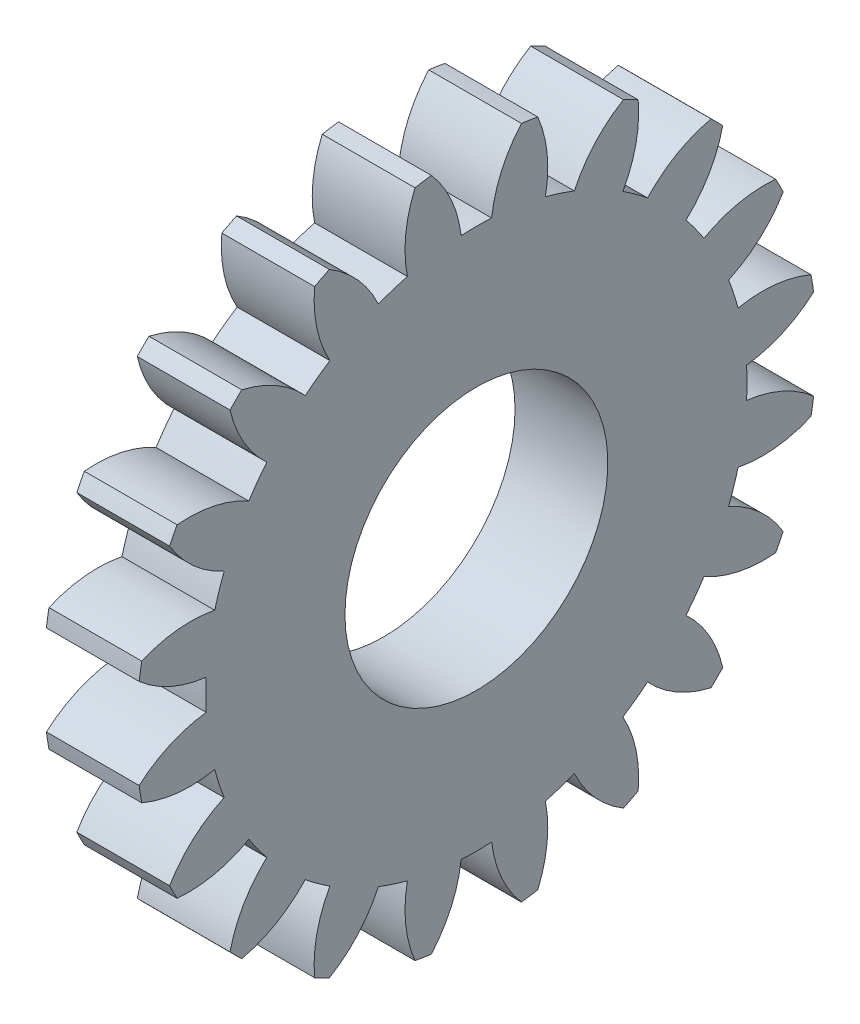
SolidWorks part; units mm, degrees
ref_plane "Plane1" through (0, 0, 0) normal (0, 0, 1) x (1, 0, 0)
ref_plane "Plane2" through (0, 0, 0) normal (0, 1, 0) x (1, 0, 0)
ref_plane "Plane3" through (0, 0, 0) normal (1, 0, 0) x (0, 0, -1)
sketch "HoldingSke" plane through (0, 0, 0) normal (0, 1, 0) x (1, 0, 0)
  line L0 (0, 0) -> (0.4698, -0.171)
  line L1 (-15, 0) -> (100, 0) construction
  line L2 (0, 0) -> (-2.1039, 2.3779)
  line L3 (0, 0) -> (-11.863, 4.5341)
  line L4 (0, 0) -> (8.1152, 2.9537)
  line L5 (0, 0) -> (-46.8476, -17.4728)
  line L6 (0, 0) -> (-4.9738, -3.3558)
  line L7 (-2.1039, 2.3779) -> (8.6586, 51.2059)
  line L8 (-76.2, 54.61) -> (-73.4, 54.61)
  line L9 (-71.009, 38.7566) -> (-53.1078, 45.2721)
  line L10 (-76.2, 71.12) -> (104.1128, 71.12)
  line L11 (0, 0) -> (-6, 0)
  line L12 (-76.2, 101.6) -> (-76.133, 101.6)
  line L13 (24.9733, 27.94) -> (52.9518, 28.4284)
  line L14 (24.9733, 27.94) -> (24.9743, 27.94)
  line L15 (24.9733, 27.94) -> (100.4006, 29.5858)
  line L16 (-63.627, -2) -> (-12.827, -2)
  circle A0 centre (0, 0) radius 8.5
  circle A1 centre (0, 0) radius 17.499
  circle A2 centre (0, 0) radius 37.5
  circle A3 centre (0, 0) radius 8.5
  dimension "Num_teeth" = 20
  dimension "Pitch_radius" = 180.3128
  dimension "Width" = 6
  dimension "Thickness" = 6
sketch "BasProSke" plane through (0, 0, 0) normal (0, 1, 0) x (1, 0, 0)
  line L0 (-10, 0) -> (60, 0) construction
  line L1 (0, 0) -> (0, 22)
  line L2 (0, 0) -> (6, 0)
  line L3 (6, 0) -> (6, 22)
  line L4 (6, 22) -> (0, 22)
  dimension "Thickness" = 6
  dimension "Diameter" = 44
revolve "Base-Revolve" add sketch "BasProSke" angle 360 about L0
sketch "TooCutSke" plane through (0, 0, 0) normal (1, 0, 0) x (0, 0, -1)
  line L1 (0, 0) -> (0, 107) construction
  line L2 (0, 0) -> (-1.6864, 19.9288) construction
  line L3 (0, 0) -> (-6.2409, 39.4033) construction
  line L4 (-1.6864, 19.9288) -> (-3.1204, 19.7016) construction
  arc A0 (0.9862, 17.4712) -> (-0.9862, 17.4712) centre (0, 0) ccw
  arc A1 (2.9329, 21.8293) -> (-2.9329, 21.8293) centre (0, 0) ccw
  circle A2 centre (0, 0) radius 20 construction
  circle A3 centre (0, 0) radius 18.7939 construction
  arc A4 (-0.9862, 17.4712) -> (-2.9329, 21.8293) centre (-8.9313, 16.536) ccw
  arc A5 (2.9329, 21.8293) -> (0.9862, 17.4712) centre (8.9313, 16.536) ccw
extrude "ToothCut" cut sketch "TooCutSke" along normal through all
fillet "Breaks" [suppressed] radius 0.04 tangent propagation no
fillet "RootFillets" [suppressed] radius 0.501
pattern_circular "TeethCuts" count 20 every 18 about axis through (-10, 0, 0) along (1, 0, 0) of "ToothCut", "RootFillets", "Breaks"
sketch "HubNeaOneSke" plane through (0, 0, 0) normal (-1, 0, 0) x (0, 0, 1)
  circle A0 centre (0, 0) radius 17.499
  dimension "Diameter" = 34.998
extrude "HubNearOne" [suppressed] add sketch "HubNeaOneSke" along normal blind 44.0001
sketch "HubNeaBotSke" plane through (0, 0, 0) normal (-1, 0, 0) x (0, 0, 1)
  circle A0 centre (0, 0) radius 17.499
  dimension "Diameter" = 34.998
extrude "HubNearBoth" [suppressed] add sketch "HubNeaBotSke" along normal blind 22
ref_plane "FarPln" through (6, 0, 0) normal (1, 0, 0) x (0, 0, -1)
sketch "HubFarSke" plane through (6, 0, 0) normal (1, 0, 0) x (0, 0, -1)
  circle A0 centre (0, 0) radius 17.499
  dimension "Diameter" = 34.998
extrude "HubFar" [suppressed] add sketch "HubFarSke" along normal blind 22
sketch "BorSke" plane through (0, 0, 0) normal (1, 0, 0) x (0, 0, -1)
  circle A0 centre (0, 0) radius 8.5
  dimension "Diameter" = 17
extrude "Bore" cut sketch "BorSke" along normal mid plane 100.0001
sketch "KeySke" plane through (0, 0, 0) normal (1, 0, 0) x (0, 0, -1)
  line L0 (-3, 0) -> (-3, 11.3)
  line L1 (-3, 11.3) -> (3, 11.3)
  line L2 (3, 11.3) -> (3, 0)
  line L3 (0, 0) -> (0, 34) construction
  line L4 (-3, 0) -> (3, 0)
  dimension "Width" = 6
extrude "Keyway" [suppressed] cut sketch "KeySke" along normal mid plane 100.0001
pattern_circular "Keyway2" [suppressed] count 2 every 90 about axis through (-10, 0, 0) along (1, 0, 0)
equation "' \"Module@HoldingSke\" = 6.35"
equation "' \"Num_teeth@HoldingSke\" = 12"
equation "' \"Ap@HoldingSke\" =  20"
equation "' \"Ap@HoldingSke\" = 20"
equation "' \"Width@HoldingSke\" = 0.5 * 25.4"
equation "' \"Hub_dia@HoldingSke\"= 1 * 25.4"
equation "' \"Hub_dia@HoldingSke\" = 1 * 25.4"
equation "' \"Overall_len@HoldingSke\" = 1.0 * 25.4"
equation "' \"Bore@HoldingSke\" = 0.75 * 25.4"
equation "' \"T_dim@HoldingSke\" = 0.1 * 25.4"
equation "' \"Width@KeySke\" = 0.25 * 25.4"
equation "' \"Show_teeth@HoldingSke\" = 13"
equation "' \"Backlash@HoldingSke\" = 0.009 * 25.4"
equation "' \"Addendum_fac@HoldingSke\" = 1.0"
equation "' \"Dedendum_fac@HoldingSke\" = 1.25"
equation "' \"Dedendum_add@HoldingSke\" = 0.00005 * 25.4"
equation "' \"Clearance_fac@HoldingSke\" = 0.25"
equation "\"Pitch@HoldingSke\" = 1 / \"Module@HoldingSke\""
equation "\"Overcut_dia@TooCutSke\" = (\"Num_teeth@HoldingSke\" + 2 * \"Addendum_fac@HoldingSke\") / \"Pitch@HoldingSke\" + 0.002 * 25.4"
equation "\"Pitch_dia@TooCutSke\" = \"Num_teeth@HoldingSke\" / \"Pitch@HoldingSke\""
equation "\"Base_dia@TooCutSke\" = \"Num_teeth@HoldingSke\" / \"Pitch@HoldingSke\" * cos((\"Ap@HoldingSke\"  * 3.14159265 / 180))"
equation "\"Root_dia@TooCutSke\" = (\"Num_teeth@HoldingSke\" + 2) / \"Pitch@HoldingSke\" - 2 * (\"Addendum_fac@HoldingSke\" + \"Dedendum_fac@HoldingSke\") / \"Pitch@HoldingSke\" - \"Dedendum_add@HoldingSke\" * 2"
equation "\"Half_ang@TooCutSke\" = 180 / \"Num_teeth@HoldingSke\""
equation "\"Half_CT@TooCutSke\" = \"Num_teeth@HoldingSke\" / \"Pitch@HoldingSke\" * sin((3.14159265 / 2 / \"Num_teeth@HoldingSke\")) / 2 - 7 * \"Backlash@HoldingSke\" / 4"
equation "\"Flank_rad@TooCutSke\" = \"Num_teeth@HoldingSke\" / \"Pitch@HoldingSke\" / 5"
equation "\"Radius@RootFillets\" = \"Clearance_fac@HoldingSke\" / \"Pitch@HoldingSke\" + \"Dedendum_add@HoldingSke\""
equation "\"Break_rad@Breaks\" = 0.02 / \"Pitch@HoldingSke\""
equation "\"Thickness@HoldingSke\" = \"Width@HoldingSke\""
equation "\"OAL@HoldingSke\" = \"Thickness@HoldingSke\""
equation "\"MHD@HoldingSke\" = (\"Num_teeth@HoldingSke\" + 2) / \"Pitch@HoldingSke\" - 2 * (\"Addendum_fac@HoldingSke\" + \"Dedendum_fac@HoldingSke\")  / \"Pitch@HoldingSke\" - \"Dedendum_add@HoldingSke\" * 2"
equation "\"MBD@HoldingSke\" = (\"Num_teeth@HoldingSke\" + 2) / \"Pitch@HoldingSke\" - 2 * (\"Addendum_fac@HoldingSke\" + \"Dedendum_fac@HoldingSke\")  / \"Pitch@HoldingSke\" - \"Dedendum_add@HoldingSke\" * 2 - 0.002 * 25.4"
equation "\"MHD@HoldingSke\" = ((sgn( \"MHD@HoldingSke\" - \"Hub_dia@HoldingSke\" )-1)*( \"MHD@HoldingSke\" - \"Hub_dia@HoldingSke\" ))/-2+ \"Hub_dia@HoldingSke\""
equation "\"MBD@HoldingSke\" = ((sgn( \"MBD@HoldingSke\" - \"Bore@HoldingSke\" )-1)*( \"MBD@HoldingSke\" - \"Bore@HoldingSke\" ))/-2+ \"Bore@HoldingSke\""
equation "\"OAL@HoldingSke\" = ((sgn( \"OAL@HoldingSke\" - \"Overall_len@HoldingSke\" )+1)*( \"OAL@HoldingSke\" - \"Overall_len@HoldingSke\" ))/2 + \"Overall_len@HoldingSke\" + 0.000002 * 25.4"
equation "\"Num_teeth@TeethCuts\" = int( \"Show_teeth@HoldingSke\" ) + 1"
equation "\"Num_teeth@TeethCuts\" = ((sgn( \"Num_teeth@TeethCuts\" - \"Num_teeth@HoldingSke\" )-1)*( \"Num_teeth@TeethCuts\" - \"Num_teeth@HoldingSke\" ))/-2+ \"Num_teeth@HoldingSke\""
equation "\"Num_teeth@TeethCuts\" = ((sgn( \"Num_teeth@TeethCuts\" - 2.0)+1)*( \"Num_teeth@TeethCuts\" - 2.0))/2 +2.0"
equation "\"Angle@TeethCuts\" = 360.0 / \"Num_teeth@HoldingSke\""
equation "\"Diameter@BasProSke\" = (\"Num_teeth@HoldingSke\" + 2 * \"Addendum_fac@HoldingSke\") / \"Pitch@HoldingSke\""
equation "\"Thickness@BasProSke\"  = \"Thickness@HoldingSke\""
equation "' \"Fillet_rad@BasProSke\" =  \"Thickness@HoldingSke\" * 0.05"
equation "' \"Fillet_rad@BasProSke\" = \"Thickness@HoldingSke\" * 0.05"
equation "\"MHD@HoldingSke\" = ((sgn( \"MHD@HoldingSke\" - \"Root_dia@TooCutSke\" )-1)*( \"MHD@HoldingSke\" - \"Root_dia@TooCutSke\" ))/-2+ \"Root_dia@TooCutSke\""
equation "\"Diameter@HubNeaOneSke\" = \"MHD@HoldingSke\""
equation "\"Length@HubNearOne\" = \"OAL@HoldingSke\" - \"Thickness@BasProSke\""
equation "\"Diameter@HubNeaBotSke\" = \"MHD@HoldingSke\""
equation "\"Length@HubNearBoth\" = ( \"OAL@HoldingSke\" - \"Thickness@BasProSke\" ) / 2.0"
equation "\"Thickness@FarPln\" = \"Thickness@BasProSke\""
equation "\"Diameter@HubFarSke\" = \"MHD@HoldingSke\""
equation "\"Length@HubFar\" = ( \"OAL@HoldingSke\" - \"Thickness@BasProSke\" ) / 2.0"
equation "\"Diameter@BorSke\" = \"MBD@HoldingSke\""
equation "\"D1@Bore\" = \"OAL@HoldingSke\" * 2.0"
equation "\"D1@Keyway\" = \"OAL@HoldingSke\" * 2.0"
equation "\"Offset@KeySke\" = \"T_dim@HoldingSke\" + \"MBD@HoldingSke\" / 2.0"
